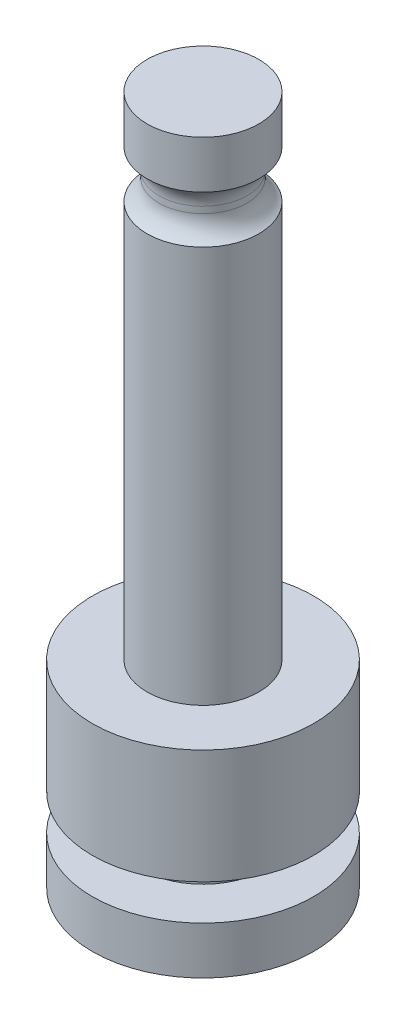
SolidWorks part; units mm, degrees
ref_plane "Front" through (0, 0, 0) normal (0, 0, 1) x (1, 0, 0)
ref_plane "Top" through (0, 0, 0) normal (0, 1, 0) x (1, 0, 0)
ref_plane "Right" through (0, 0, 0) normal (1, 0, 0) x (0, 0, -1)
sketch "Sketch1" plane through (0, 0, 0) normal (0, 1, 0) x (1, 0, 0)
  circle A0 centre (0, 0) radius 4.65
  dimension "D1" = 9.3
extrude "Boss-Extrude1" add sketch "Sketch1" along normal blind 4.3 and the other way blind 4
sketch "Sketch2" plane through (0, 4.3, 0) normal (0, 1, 0) x (1, 0, 0)
  circle A0 centre (0, 0) radius 2.35
  dimension "D1" = 4.7
extrude "Boss-Extrude2" add sketch "Sketch2" along normal blind 20.68
sketch "Sketch3" plane through (0, 24.98, 0) normal (0, 1, 0) x (1, 0, 0)
  circle A0 centre (0, 0) radius 1.85
  circle A2 centre (0, 0) radius 2.35
  circle A3 centre (0, 0) radius 2.35
  point P3 (0, 0)
  dimension "D2" = 0.5
  dimension "D1" = 0
extrude "Cut-Extrude1" cut sketch "Sketch3" against normal blind 2 from offset 2 offset against normal yes
sketch "Sketch4" plane through (0, -4, 0) normal (0, -1, 0) x (1, 0, 0)
  circle A0 centre (0, 0) radius 2.65
  circle A1 centre (0, 0) radius 4.65
  circle A2 centre (0, 0) radius 4.65
  dimension "D2" = 2
  dimension "D1" = 0
extrude "Cut-Extrude2" cut sketch "Sketch4" against normal blind 1.5 from offset 2 offset against normal yes
fillet "Fillet1" radius 1 2 edges at (0, 20.98, 1.85) (0, 22.98, 1.85)
